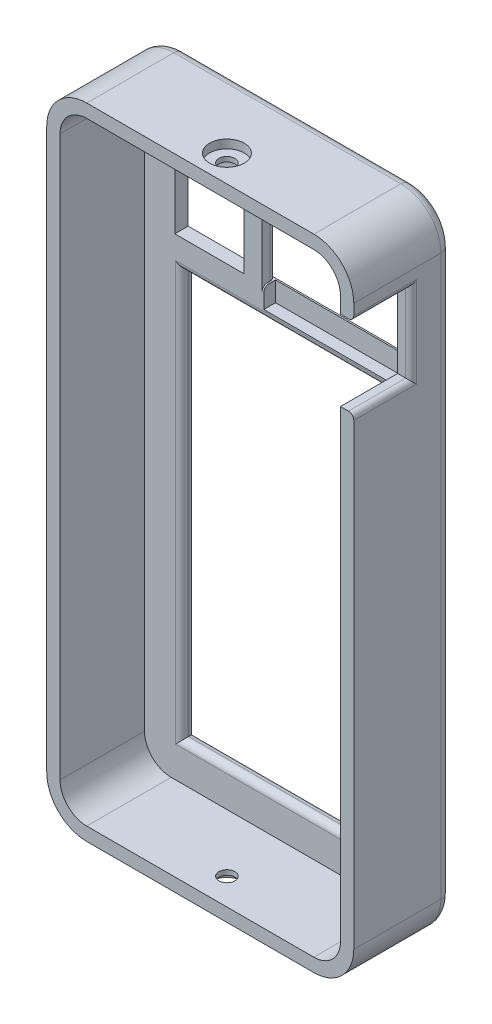
SolidWorks part; units mm, degrees
ref_plane "Front Plane" through (0, 0, 0) normal (0, 0, 1) x (1, 0, 0)
ref_plane "Top Plane" through (0, 0, 0) normal (0, 1, 0) x (1, 0, 0)
ref_plane "Right Plane" through (0, 0, 0) normal (1, 0, 0) x (0, 0, -1)
sketch "Sketch1" plane through (0, 0, 0) normal (0, 0, 1) x (1, 0, 0)
  line L24 (15.6157, 54.5139) -> (58.1937, 54.5139)
  line L25 (65.6937, 62.0139) -> (65.6937, 166.9489)
  line L26 (8.1157, 166.9489) -> (8.1157, 62.0139)
  line L27 (58.1937, 174.4489) -> (15.6157, 174.4489)
  line L28 (15.6157, 54.5139) -> (58.1937, 54.5139)
  line L29 (65.6937, 62.0139) -> (65.6937, 166.9489)
  line L30 (8.1157, 166.9489) -> (8.1157, 62.0139)
  line L31 (58.1937, 174.4489) -> (15.6157, 174.4489)
  arc A20 (8.1157, 62.0139) -> (15.6157, 54.5139) centre (15.6157, 62.0139) ccw
  arc A21 (58.1937, 54.5139) -> (65.6937, 62.0139) centre (58.1937, 62.0139) ccw
  arc A22 (65.6937, 166.9489) -> (58.1937, 174.4489) centre (58.1937, 166.9489) ccw
  arc A23 (15.6157, 174.4489) -> (8.1157, 166.9489) centre (15.6157, 166.9489) ccw
  arc A24 (8.1157, 62.0139) -> (15.6157, 54.5139) centre (15.6157, 62.0139) ccw
  arc A25 (58.1937, 54.5139) -> (65.6937, 62.0139) centre (58.1937, 62.0139) ccw
  arc A26 (65.6937, 166.9489) -> (58.1937, 174.4489) centre (58.1937, 166.9489) ccw
  arc A27 (15.6157, 174.4489) -> (8.1157, 166.9489) centre (15.6157, 166.9489) ccw
  dimension "D1" = 2.5
extrude "Boss-Extrude1" add sketch "Sketch1" against normal offset from surface (18.3324 mm away) 8 offset beyond the face yes
shell "Shell2" thickness 2.5 removed face at (36.9047, 114.4814, 0)
sketch "Sketch2" plane through (0, 0, -18.3324) normal (0, 0, -1) x (-1, 0, 0)
  line L1 (-33.4793, 169.0868) -> (-39.6793, 169.0868) construction
  line L2 (-32.6793, 145.3868) -> (-59.3793, 145.3868)
  line L3 (-32.6793, 145.3868) -> (-32.6793, 164.4868)
  line L4 (-32.6793, 164.4868) -> (-59.3793, 164.4868)
  line L5 (-59.3793, 145.3868) -> (-59.3793, 164.4868)
  line L6 (-32.9793, 142.1868) -> (-32.9793, 168.5868) construction
  line L7 (-61.3793, 168.5868) -> (-61.3793, 142.1868) construction
  line L8 (-60.8793, 141.6868) -> (-33.4793, 141.6868) construction
  line L9 (-29.3022, 159.6316) -> (-16.3022, 159.6316)
  line L14 (-29.3022, 159.6316) -> (-29.3022, 145.6316)
  line L15 (-29.3022, 145.6316) -> (-16.3022, 145.6316)
  line L16 (-16.3022, 159.6316) -> (-16.3022, 145.6316)
  line L17 (-8.1157, 62.0139) -> (-8.1157, 166.9489) construction
  line L18 (-56.1937, 140.1868) -> (-17.6157, 140.1868)
  line L19 (-56.1937, 140.1868) -> (-56.1937, 64.0139)
  line L20 (-56.1937, 64.0139) -> (-17.6157, 64.0139)
  line L21 (-17.6157, 140.1868) -> (-17.6157, 64.0139)
  line L22 (-65.6937, 166.9489) -> (-65.6937, 62.0139) construction
  line L23 (-58.1937, 54.5139) -> (-15.6157, 54.5139) construction
  dimension "D1" = 13
  dimension "D2" = 4.6
  dimension "D3" = 0.3
  dimension "D4" = 2
  dimension "D5" = 3.7
  dimension "D6" = 9.5
  dimension "D7" = 9.5
  dimension "D8" = 5.2
  dimension "D9" = 9.5
  dimension "D10" = 14
extrude "Cut-Extrude1" cut sketch "Sketch2" against normal blind 4
fillet "Fillet1" radius 2 8 edges at (10.3124, 172.2522, -18.3324) (8.1157, 114.4814, -18.3324) (10.3124, 56.7106, -18.3324) (36.9047, 54.5139, -18.3324) (63.497, 56.7106, -18.3324) (65.6937, 114.4814, -18.3324) (63.497, 172.2522, -18.3324) (36.9047, 174.4489, -18.3324)
fillet "Fillet2" radius 1.2 8 edges at (36.9047, 140.1868, -18.3324) (36.9047, 64.0139, -15.8324) (17.6157, 102.1003, -15.8324) (36.9047, 64.0139, -18.3324) (17.6157, 102.1003, -18.3324) (36.9047, 140.1868, -15.8324) (56.1937, 102.1003, -15.8324) (56.1937, 102.1003, -18.3324)
fillet "Fillet4" radius 1 5 edges at (46.0293, 164.4868, -15.8324) (46.0293, 145.3868, -15.8324) (59.3793, 154.9368, -18.3324) (32.6793, 154.9368, -18.3324) (46.0293, 164.4868, -18.3324)
sketch "Sketch3" plane through (65.6937, 0, 0) normal (1, 0, 0) x (0, 0, -1)
  line L0 (0, 62.0139) -> (0, 166.9489) construction
  line L1 (0, 163.9489) -> (10.7324, 163.9489)
  line L2 (0, 163.9489) -> (0, 148.9489)
  line L3 (0, 148.9489) -> (10.7324, 148.9489)
  line L4 (10.7324, 163.9489) -> (10.7324, 148.9489)
  line L5 (16.3324, 166.9489) -> (0, 166.9489) construction
  line L6 (18.3324, 166.9489) -> (18.3324, 62.0139) construction
  point P8 (8.1662, 166.9489)
  dimension "D1" = 15
  dimension "D2" = 3
  dimension "D3" = 7.6
extrude "Cut-Extrude2" cut sketch "Sketch3" against normal up to next
fillet "Fillet5" radius 1 3 edges at (65.6937, 156.4489, -10.7324) (65.6937, 163.9489, -5.3662) (65.6937, 148.9489, -5.3662)
sketch "Sketch6" plane through (0, 0, -15.8324) normal (0, 0, 1) x (1, 0, 0)
  line L0 (32.9793, 142.1868) -> (32.9793, 168.5868) construction
  line L1 (59.4533, 169.0868) -> (32.9793, 169.0868)
  line L2 (59.4533, 169.0868) -> (59.4533, 141.6868)
  line L3 (59.4533, 141.6868) -> (32.9793, 141.6868)
  line L4 (32.9793, 169.0868) -> (32.9793, 141.6868)
  line L5 (54.6793, 169.0868) -> (60.8793, 169.0868) construction
  line L6 (60.8793, 141.6868) -> (33.4793, 141.6868) construction
  dimension "D1" = 0
  dimension "D2" = 0
  dimension "D3" = 0
  dimension "D4" = 0
extrude "Cut-Extrude5" cut sketch "Sketch6" against normal blind 2.2
sketch "Sketch7" plane through (0, 174.4489, 0) normal (0, 1, 0) x (1, 0, 0)
  circle A0 centre (36.9047, 5) radius 3.25
  dimension "D1" = 6.5
extrude "Cut-Extrude6" cut sketch "Sketch7" against normal blind 1.6
sketch "Sketch8" plane through (0, 54.5139, 0) normal (0, -1, 0) x (1, 0, 0)
  circle A0 centre (36.9047, -5) radius 3.25
  dimension "D1" = 6.5
extrude "Cut-Extrude7" cut sketch "Sketch8" against normal blind 1.6
sketch "Sketch9" plane through (0, 56.1139, 0) normal (0, -1, 0) x (1, 0, 0)
  circle A0 centre (36.9047, -5) radius 1.5
  dimension "D1" = 3
extrude "Cut-Extrude8" cut sketch "Sketch9" against normal blind 5
sketch "Sketch10" plane through (0, 172.8489, 0) normal (0, 1, 0) x (1, 0, 0)
  circle A0 centre (36.9047, 5) radius 1.5
  dimension "D1" = 3
extrude "Cut-Extrude9" cut sketch "Sketch10" against normal blind 5
